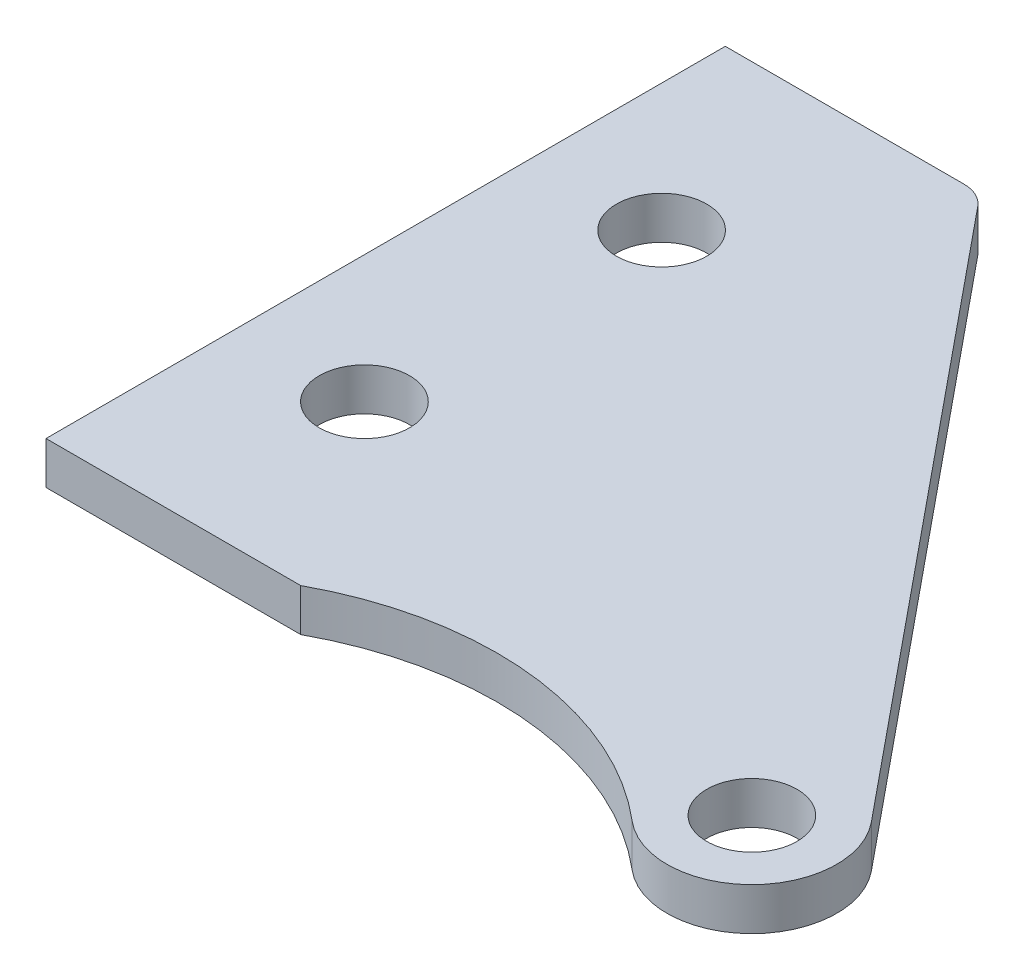
SolidWorks part; units mm, degrees
material "6061-T6 (SS)"
ref_plane "Front" through (0, 0, 0) normal (0, 0, 1) x (1, 0, 0)
ref_plane "Top" through (0, 0, 0) normal (0, 1, 0) x (1, 0, 0)
ref_plane "Right" through (0, 0, 0) normal (1, 0, 0) x (0, 0, -1)
sketch "Sketch1" plane through (0, 0, 0) normal (0, 1, 0) x (1, 0, 0)
  line L1 (0, 50.8) -> (19.05, 50.8)
  line L3 (19.05, 50.8) -> (55.7137, 6.0089)
  line L4 (0, 50.8) -> (0, 0)
  line L6 (0, 0) -> (19.05, 0)
  arc A0 (55.7137, 6.0089) -> (46.6945, -2.8575) centre (50.8, 1.9868) cw
  arc A3 (19.05, 0) -> (46.6945, -2.8575) centre (30.784, -21.6311) cw
  dimension "D1" = 19.05
  dimension "D3" = 6.35
  dimension "D4" = 50.8
  dimension "D5" = 50.8
extrude "Boss-Extrude1" add sketch "Sketch1" along normal blind 3.175
hole_wizard "1/4 Clearance Hole2" positions "Sketch4" profile "Sketch3" hole size "1/4" standard "ANSI Inch" end condition through all
sketch "Sketch4" plane through (0, 0, 0) normal (0, -1, 0) x (-1, 0, 0)
  point P0 (-50.8, 1.9868)
sketch "Sketch3" plane through (50.8, 0, -1.9868) normal (1, 0, 0) x (0, 0, -1)
  line L0 (0, 0) -> (0, 3.175)
  line L1 (0, 3.175) -> (3.3782, 3.175)
  line L2 (3.3782, 3.175) -> (3.3782, 0)
  line L5 (3.3782, 0) -> (0, 0)
  line L11 (0, -6.35) -> (0, 107.95) construction
  dimension "Thru Hole Dia." = 6.7564
  dimension "Thru Hole Depth" = 3.175
hole_wizard "1/4 Clearance Hole1" positions "Sketch7" profile "Sketch8" hole size "1/4" standard "ANSI Inch" end condition through all
sketch "Sketch7" plane through (0, 3.175, 0) normal (0, 1, 0) x (1, 0, 0)
  line L9 (9.525, 0) -> (9.525, 14.2875) construction
  line L10 (0, 0) -> (19.05, 0) construction
  line L11 (9.525, 14.2875) -> (9.525, 36.5125) construction
  line L12 (9.525, 36.5125) -> (9.525, 50.8) construction
  line L13 (19.05, 50.8) -> (0, 50.8) construction
  point P0 (9.525, 36.5125)
  point P2 (9.525, 14.2875)
  dimension "D1" = 22.225
sketch "Sketch8" plane through (9.525, 3.175, -36.5125) normal (1, 0, 0) x (0, 0, 1)
  line L0 (0, 0) -> (0, 3.175)
  line L1 (0, 3.175) -> (3.3782, 3.175)
  line L2 (3.3782, 3.175) -> (3.3782, 0)
  line L5 (3.3782, 0) -> (0, 0)
  line L11 (0, -6.35) -> (0, 107.95) construction
  dimension "Thru Hole Dia." = 6.7564
  dimension "Thru Hole Depth" = 3.175
fillet "Fillet1" radius 2.54 1 edges at (19.05, 1.5875, -50.8)
